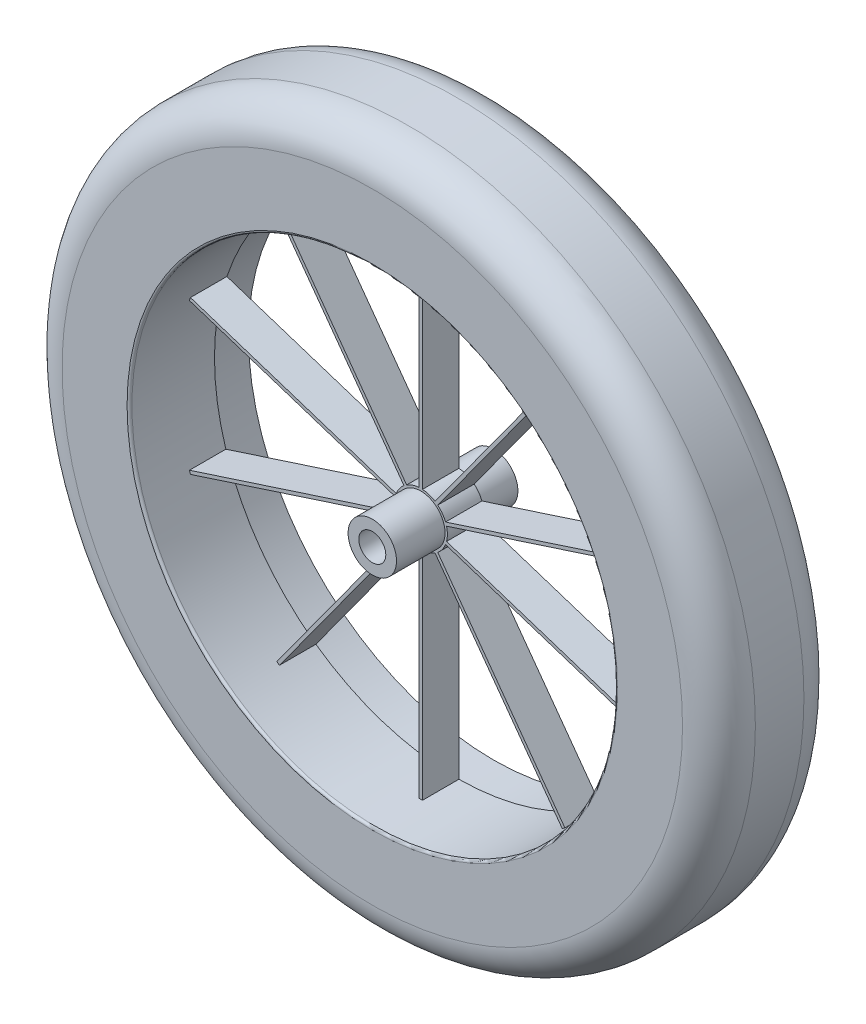
SolidWorks part; units mm, degrees
ref_plane "Alzado" through (0, 0, 0) normal (0, 0, 1) x (1, 0, 0)
ref_plane "Planta" through (0, 0, 0) normal (0, 1, 0) x (1, 0, 0)
ref_plane "Vista lateral" through (0, 0, 0) normal (1, 0, 0) x (0, 0, -1)
sketch "Croquis1" plane through (0, 0, 0) normal (0, 0, 1) x (1, 0, 0)
  circle A0 centre (0, 0) radius 275
  dimension "D1" = 550
extrude "Saliente-Extruir1" add sketch "Croquis1" along normal blind 70
sketch "Croquis2" plane through (0, 0, 70) normal (0, 0, 1) x (1, 0, 0)
  circle A0 centre (0, 0) radius 200
  dimension "D1" = 400
extrude "Cortar-Extruir1" cut sketch "Croquis2" against normal blind 40
sketch "Croquis5" plane through (0, 0, 30) normal (0, 0, 1) x (1, 0, 0)
  circle A0 centre (0, 0) radius 10
  dimension "D1" = 20
extrude "Cortar-Extruir2" cut sketch "Croquis5" against normal blind 10
fillet "Redondeo1" radius 2 1 edges at (200, 0, 70)
sketch "Croquis6" plane through (0, 0, 70) normal (0, 0, 1) x (1, 0, 0)
  line L0 (0, 275) -> (0, 247)
  line L1 (99.3415, 256.4299) -> (89.2267, 230.3206)
  line L2 (185.2663, 203.2275) -> (166.4028, 182.5352)
  line L3 (246.1699, 122.578) -> (221.1053, 110.0974)
  line L4 (273.8269, 25.3738) -> (245.9463, 22.7903)
  line L5 (264.5021, -75.2573) -> (237.5709, -67.5948)
  line L6 (219.4547, -165.7245) -> (197.1103, -148.8508)
  line L7 (144.7688, -233.8097) -> (130.0287, -210.0036)
  line L8 (50.5311, -270.3176) -> (45.3861, -242.7944)
  line L9 (-50.5311, -270.3176) -> (-45.3861, -242.7944)
  line L10 (-144.7688, -233.8097) -> (-130.0287, -210.0036)
  line L11 (-219.4547, -165.7245) -> (-197.1103, -148.8508)
  line L12 (-264.5021, -75.2573) -> (-237.5709, -67.5948)
  line L13 (-273.8269, 25.3738) -> (-245.9463, 22.7903)
  line L14 (-246.1699, 122.578) -> (-221.1053, 110.0974)
  line L15 (-185.2663, 203.2275) -> (-166.4028, 182.5352)
  line L16 (-99.3415, 256.4299) -> (-89.2267, 230.3206)
  circle A0 centre (0, 0) radius 275 construction
  point P40 (0, 0)
  dimension "D2" = 28
  dimension "D1" = 17
extrude "Cortar-Extruir-Lámina2" cut sketch "Croquis6" against normal through all thin contours L16 thin type one direction wall 0.1
pattern_circular "MatrizC1" count 24 every 15 about axis through (0, 0, 20) along (0, 0, 1) of "Cortar-Extruir-Lámina2" reverse direction yes
sketch "Croquis11" plane through (0, 0, 30) normal (0, 0, 1) x (1, 0, 0)
  line L0 (207.6044, 68.8646) -> (-208.433, -66.3142)
  line L1 (-1.3408, 218.7238) -> (1.3408, 218.7238)
  line L2 (-1.3408, 218.7238) -> (-1.3408, -218.7238)
  line L3 (-1.3408, -218.7238) -> (1.3408, -218.7238)
  line L4 (1.3408, 218.7238) -> (1.3408, -218.7238)
  line L5 (-1.3408, 218.7238) -> (1.3408, -218.7238) construction
  line L6 (-1.3408, -218.7238) -> (1.3408, 218.7238) construction
  line L7 (208.433, 66.3142) -> (-207.6044, -68.8646)
  line L8 (129.6474, -176.1632) -> (-127.4779, 177.7394)
  line L9 (127.4779, -177.7394) -> (-129.6474, 176.1632)
  line L10 (-127.4779, -177.7394) -> (129.6474, 176.1632)
  line L11 (-129.6474, -176.1632) -> (127.4779, 177.7394)
  line L12 (-208.433, 66.3142) -> (207.6044, -68.8646)
  line L13 (-207.6044, 68.8646) -> (208.433, -66.3142)
  circle A0 centre (0, 0) radius 21.8489
  circle A1 centre (0, 0) radius 200 construction
  circle A2 centre (0, 0) radius 200
  point P27 (0, 0)
  circle M2 centre (0, 0) radius 200
  dimension "D1" = 5
extrude "Cortar-Extruir3" cut sketch "Croquis11" against normal blind 150 contours A0 L9 L13 M2 | A0 L2 L8 M2 | A0 L11 L4 M2 | A0 L0 L10 M2 | A0 L13 L7 M2 | A0 L8 L12 M2 | A0 L12 L0 M2 | A0 L7 L11 M2 | A0 L10 L2 M2 | A0 L4 L9 M2 region at (108.1147, 78.5499, 30) region at (133.6371, 0, 30) region at (41.2961, 127.0964, 30) region at (108.1147, -78.5499, 30) region at (-41.2961, 127.0964, 30) region at (41.2961, -127.0964, 30) region at (-108.1147, 78.5499, 30) region at (-41.2961, -127.0964, 30) region at (-133.6371, 0, 30) region at (-108.1147, -78.5499, 30)
sketch "Croquis12" plane through (0, 0, 20) normal (0, 0, 1) x (1, 0, 0)
  circle A3 centre (0, 0) radius 19.935
extrude "Saliente-Extruir2" add sketch "Croquis12" along normal blind 50 and the other way blind 50
sketch "Croquis14" plane through (0, 0, 70) normal (0, 0, 1) x (1, 0, 0)
  circle A0 centre (0, 0) radius 285.5468
  circle A1 centre (0, 0) radius 202 construction
  circle A2 centre (0, 0) radius 202
extrude "Saliente-Extruir3" add sketch "Croquis14" against normal blind 100
fillet "Redondeo2" radius 30 1 edges at (285.5468, 0, 70) tangent propagation no
fillet "Redondeo3" radius 30 1 edges at (285.5468, 0, -30)
scale "Scale1" scale about centroid uniform scaling yes scale factor 0.5
scale "Scale2" scale about centroid uniform scaling yes scale factor 0.1
scale "Scale3" scale about centroid uniform scaling yes scale factor 0.2
scale "Scale4" scale about centroid uniform scaling yes scale factor 0.3
scale "Scale5" scale about centroid uniform scaling yes scale factor 20
scale "Scale6" scale about centroid uniform scaling yes scale factor 1.5
sketch "Sketch1" plane through (0, 0, 24.6335) normal (0, 0, 1) x (1, 0, 0)
  circle A0 centre (0, 0) radius 1
  dimension "D1" = 2
extrude "Cut-Extrude1" cut sketch "Sketch1" against normal blind 5
